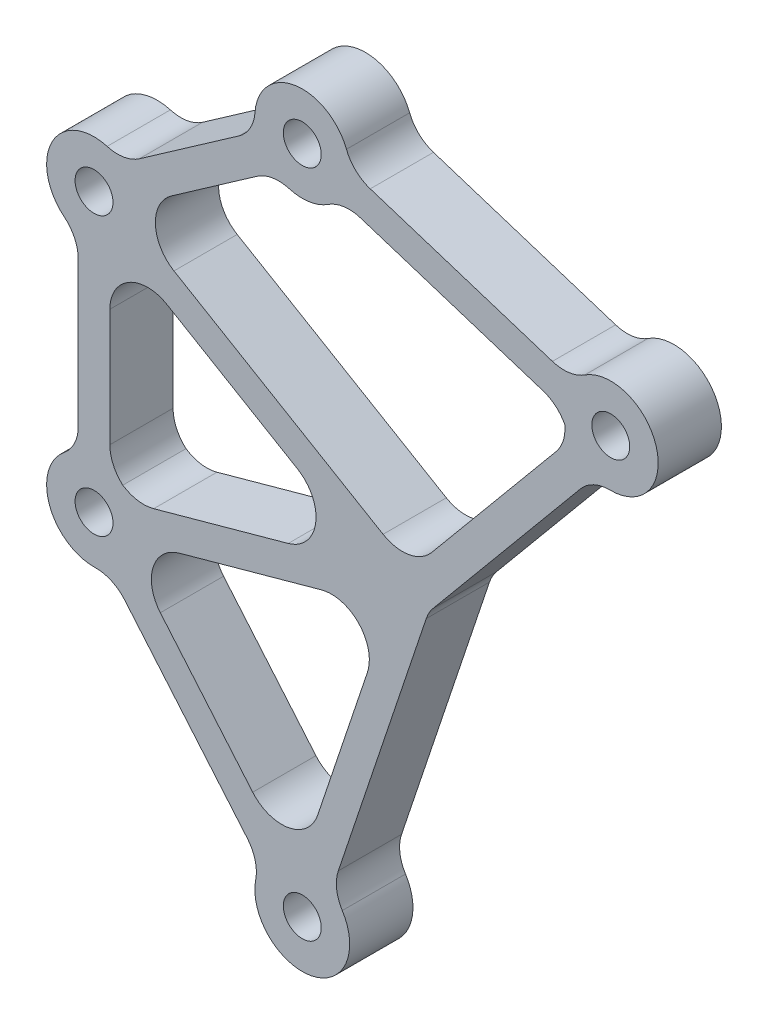
SolidWorks part; units mm, degrees
ref_plane "Front Plane" through (0, 0, 0) normal (0, 0, 1) x (1, 0, 0)
ref_plane "Top Plane" through (0, 0, 0) normal (0, 1, 0) x (1, 0, 0)
ref_plane "Right Plane" through (0, 0, 0) normal (1, 0, 0) x (0, 0, -1)
sketch "Sketch1" plane through (0, 0, 0) normal (0, 0, 1) x (1, 0, 0)
  line L0 (106.1892, 23.71) -> (75.2051, 33.6273) construction
  line L1 (75.2051, 33.6273) -> (54.2892, 19.01) construction
  line L2 (54.2892, 19.01) -> (54.2892, -8.89) construction
  line L3 (54.2892, -8.89) -> (75.2051, -33.6273) construction
  line L4 (86.4702, 0) -> (54.2892, -8.89) construction
  line L5 (54.2892, 19.01) -> (86.4702, 0) construction
  line L6 (86.4702, 0) -> (75.2051, -33.6273) construction
  line L8 (106.1892, 23.71) -> (86.4702, 0) construction
  line L9 (121.1912, 0) -> (51.7492, 0) construction
  line L10 (51.7492, -26.63) -> (51.7492, 26.63) construction
  line L11 (102.3967, 26.5907) -> (79.9654, 33.7704)
  line L13 (101.4289, 23.5668) -> (78.9976, 30.7465)
  line L15 (72.434, 29.7539) -> (58.879, 20.2809)
  line L17 (70.6153, 32.3564) -> (57.0603, 22.8833)
  line L19 (52.7017, 14.5199) -> (52.7017, -4.3999)
  line L21 (55.8767, 14.5199) -> (55.8767, -4.3999)
  line L23 (58.4006, -11.2938) -> (73.5183, -29.1735)
  line L25 (55.9761, -13.3438) -> (71.0937, -31.2235)
  line L27 (102.0975, 21.2729) -> (86.1139, 2.0543)
  line L28 (86.1139, 2.0543) -> (58.9626, 18.0931)
  line L30 (57.3478, 15.3594) -> (82.4438, 0.5347)
  line L31 (82.4438, 0.5347) -> (58.1945, -6.1642)
  line L33 (59.0399, -9.2246) -> (84.0172, -2.3246)
  line L34 (84.0172, -2.3246) -> (75.1261, -28.8654)
  line L36 (104.5386, 19.2427) -> (87.881, -0.7864)
  line L37 (87.881, -0.7864) -> (78.1367, -29.874)
  circle A0 centre (54.2892, 19.01) radius 1.905
  circle A1 centre (54.2892, 19.01) radius 4.7625
  circle A2 centre (54.2892, -8.89) radius 1.905
  circle A3 centre (54.2892, -8.89) radius 4.7625
  circle A6 centre (75.2051, 33.6273) radius 4.7625
  circle A7 centre (75.2051, -33.6273) radius 4.7625
  circle A8 centre (75.2051, -33.6273) radius 1.905
  circle A9 centre (75.2051, 33.6273) radius 1.905
  circle A10 centre (106.1892, 23.71) radius 1.905
  circle A11 centre (106.1892, 23.71) radius 4.7625
  circle A12 centre (87.6662, 15) radius 3 construction
  circle A13 centre (87.6662, -15) radius 3 construction
  point P60 (82.1916, 0.5355)
  point P61 (84.336, 0)
  dimension "D1" = 3.81
  dimension "D2" = 9.525
  dimension "D11" = 6
  dimension "D3" = 1.5875
  dimension "D4" = 1.5875
  dimension "D5" = 1.5875
  dimension "D6" = 1.5875
  dimension "D7" = 1.5875
  dimension "D8" = 1.5875
  dimension "D9" = 1.5875
  dimension "D10" = 1.5875
extrude "Boss-Extrude1" add sketch "Sketch1" along normal blind 6.35 contours A11 A10 | A11 L27 L28 A1 L30 L31 A3 L33 L34 A7 L37 L36 | A11 L11 A6 L13 | A6 A9 | A6 L17 A1 L15 | A1 A0 | A3 L21 A1 L19 | A3 A2 | A7 L23 A3 L25 | A7 A8 region at (90.6972, 28.6686, 0) region at (107.666, 28.0958, 0) region at (79.8324, 33.6968, 0) region at (64.7472, 26.3186, 0) region at (95.6747, 9.6731, 0) region at (58.0825, 21.661, 0) region at (54.2892, 5.06, 0) region at (79.3644, -31.5983, 0) region at (54.2892, -4.2622, 0) region at (64.7472, -21.2586, 0)
fillet "Fillet1" radius 3.81 28 edges at (58.9626, 18.0931, 3.175) (86.1139, 2.0543, 3.175) (102.0975, 21.2729, 3.175) (101.4289, 23.5668, 3.175) (78.9976, 30.7465, 3.175) (72.434, 29.7539, 3.175) (58.879, 20.2809, 3.175) (73.5183, -29.1735, 3.175) (75.1261, -28.8654, 3.175) (84.0172, -2.3246, 3.175) (59.0399, -9.2246, 3.175) (58.4006, -11.2938, 3.175) (55.8767, -4.3999, 3.175) (58.1945, -6.1642, 3.175) (82.4438, 0.5347, 3.175) (57.3478, 15.3594, 3.175) (55.8767, 14.5199, 3.175) (79.9654, 33.7704, 3.175) (102.3967, 26.5907, 3.175) (104.5386, 19.2427, 3.175) (87.881, -0.7864, 3.175) (78.1367, -29.874, 3.175) (71.0937, -31.2235, 3.175) (55.9761, -13.3438, 3.175) (52.7017, -4.3999, 3.175) (52.7017, 14.5199, 3.175) (57.0603, 22.8833, 3.175) (70.6153, 32.3564, 3.175)
fillet "Fillet2" radius 3.81 4 edges at (74.2787, -28.7925, 3.175) (59.1136, 19.1944, 3.175) (58.9049, -10.3162, 3.175) (56.7234, 14.7449, 3.175)
